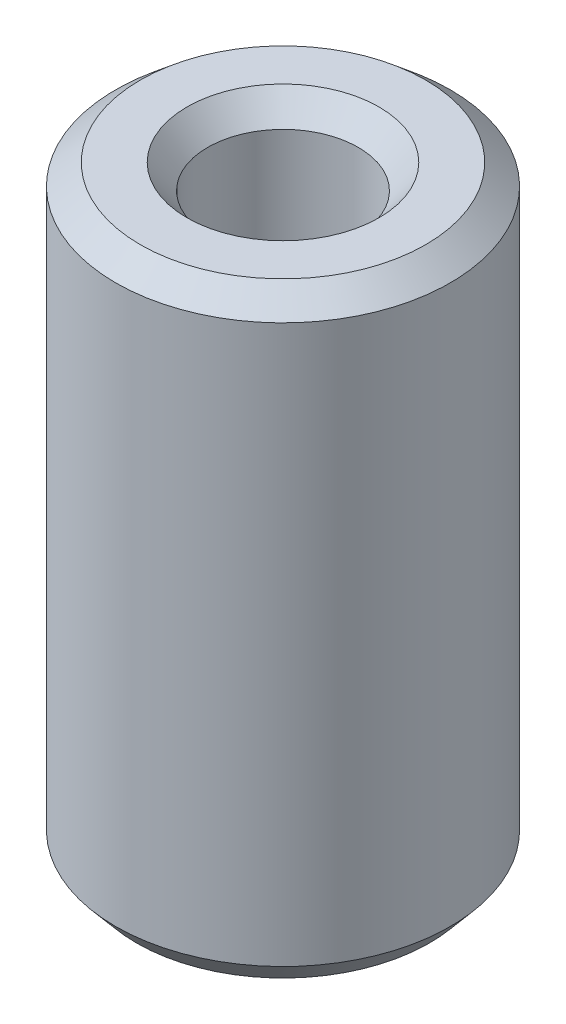
SolidWorks part; units mm, degrees
ref_plane "Front Plane" through (0, 0, 0) normal (0, 0, 1) x (1, 0, 0)
ref_plane "Top Plane" through (0, 0, 0) normal (0, 1, 0) x (1, 0, 0)
ref_plane "Right Plane" through (0, 0, 0) normal (1, 0, 0) x (0, 0, -1)
sketch "Sketch1" plane through (0, 0, 0) normal (0, 1, 0) x (1, 0, 0)
  circle A0 centre (0, 0) radius 5
  dimension "SLEEVE_OD" = 10
extrude "Boss-Extrude1" add sketch "Sketch1" along normal blind 18.0155
sketch "Sketch2" plane through (0, 0, 0) normal (0, 1, 0) x (1, 0, 0)
  circle A0 centre (0, 0) radius 2.2506
  dimension "BORE_D" = 4.5013
extrude "Cut-Extrude1" cut sketch "Sketch2" along normal through all
chamfer "Chamfer1" distance 0.6194 angle 49.922 4 edges at (0, 18.0155, 2.2506) (0, 0, 2.2506) (0, 0, 5) (0, 18.0155, 5) first distance on face at (0, 18.0155, 2.2506) first distance on face at (0, 0, 2.2506) first distance on face at (0, 18.0155, 5)
